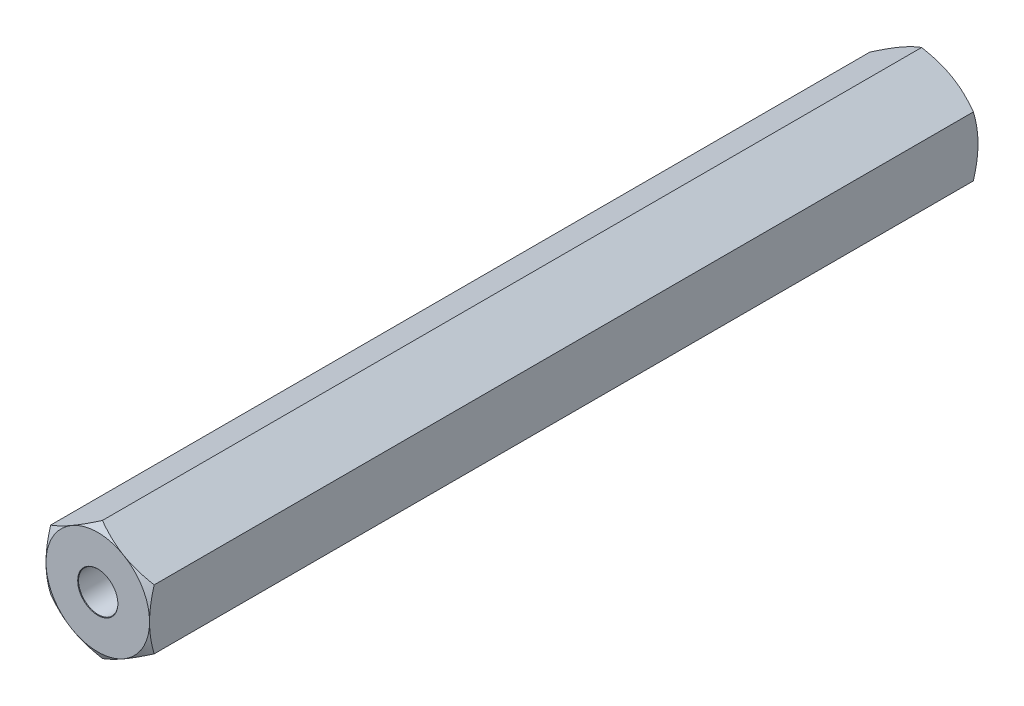
SolidWorks part; units mm, degrees
material "2011 Alloy"
ref_plane "Front Plane" through (0, 0, 0) normal (0, 0, 1) x (1, 0, 0)
ref_plane "Top Plane" through (0, 0, 0) normal (0, 1, 0) x (1, 0, 0)
ref_plane "Right Plane" through (0, 0, 0) normal (1, 0, 0) x (0, 0, -1)
sketch "Sketch3" plane through (0, 0, 0) normal (1, 0, 0) x (0, 0, -1)
  line L0 (-50.8, 0) -> (50.8, 0) construction
  line L1 (0, 6.35) -> (0, -6.35) construction
  line L2 (-50.8, 2.413) -> (-50.8, -2.413) construction
  point P2 (38.1, 0)
  point P3 (-38.1, 0)
  dimension "Length" = 101.6
  dimension "Min Thread Length" = 12.7
  dimension "D1" = 12.7
  dimension "Thread Dia" = 4.826
  dimension "Hex" = 12.7
sketch "Sketch1" plane through (0, 0, 0) normal (0, 0, 1) x (1, 0, 0)
  line L1 (0, 7.3323) -> (-6.35, 3.6662)
  line L2 (-6.35, 3.6662) -> (-6.35, -3.6662)
  line L3 (-6.35, -3.6662) -> (0, -7.3323)
  line L4 (0, -7.3323) -> (6.35, -3.6662)
  line L5 (6.35, -3.6662) -> (6.35, 3.6662)
  line L6 (6.35, 3.6662) -> (0, 7.3323)
  circle A0 centre (0, 0) radius 6.35 construction
  circle A1 centre (0, 0) radius 2.413
extrude "Extrude1" add sketch "Sketch1" along normal up to vertex (50.8 mm away) and the other way up to vertex (50.8 mm away) up to point (0, 0, 50.8) other way up to point (0, 0, -50.8)
sketch "Sketch11" plane through (0, 0, -50.8) normal (0, 0, -1) x (-1, 0, 0)
  circle A0 centre (0, 0) radius 2.413 construction
  circle A1 centre (0, 0) radius 2.413
curve "Helix/Spiral1" pitch 0.7937 height 102.3937 turns 129 parameters "Pitch"=0.7937
sketch "Sketch12" plane through (0, 0, 0) normal (1, 0, 0) x (0, 0, -1)
  line L0 (51.4945, 2.413) -> (50.8, 2.413)
  line L1 (51.4945, 2.413) -> (51.1969, 1.8974)
  line L2 (51.1969, 1.8974) -> (51.0977, 1.8974)
  line L3 (51.0977, 1.8974) -> (50.8, 2.413)
  line L4 (51.1473, 1.8974) -> (51.1473, 2.413) construction
  line L5 (51.3457, 2.1552) -> (50.9488, 2.1552) construction
  dimension "D1" = 0.0992
  dimension "D2" = 0.3969
  dimension "D3" = 60
sweep "Sweep1" [suppressed] add profiles "Sketch12" path "Helix/Spiral1"
sketch "Sketch6" plane through (0, 0, -50.8) normal (0, 0, -1) x (-1, 0, 0)
  line L6 (0, 7.3323) -> (-6.35, 3.6662)
  line L7 (-6.35, 3.6662) -> (-6.35, -3.6662)
  line L8 (-6.35, -3.6662) -> (0, -7.3323)
  line L9 (0, -7.3323) -> (6.35, -3.6662)
  line L10 (6.35, -3.6662) -> (6.35, 3.6662)
  line L11 (6.35, 3.6662) -> (0, 7.3323)
  line L12 (0, 7.3323) -> (-6.35, 3.6662)
  line L13 (-6.35, 3.6662) -> (-6.35, -3.6662)
  line L14 (-6.35, -3.6662) -> (0, -7.3323)
  line L15 (0, -7.3323) -> (6.35, -3.6662)
  line L16 (6.35, -3.6662) -> (6.35, 3.6662)
  line L17 (6.35, 3.6662) -> (0, 7.3323)
  dimension "D1" = 0
extrude "Extrude2" [suppressed] cut sketch "Sketch6" along normal through all
sketch "Sketch7" plane through (0, 0, -50.8) normal (0, 0, -1) x (-1, 0, 0)
  circle A2 centre (0, 0) radius 2.4638
  circle A3 centre (0, 0) radius 2.4638
  dimension "D1" = 0.0508
extrude "Extrude3" cut sketch "Sketch7" against normal through all draft 43
sketch "Sketch8" plane through (0, 0, -50.8) normal (0, 0, -1) x (-1, 0, 0)
  circle A0 centre (0, 0) radius 6.35 construction
  circle A1 centre (0, 0) radius 6.35
extrude "Extrude4" cut sketch "Sketch8" against normal through all draft 60 flip side to cut
mirror "Mirror1" about plane through (0, 0, 0) normal (0, 0, 1) of "Extrude2", "Extrude3", "Extrude4"
sketch "Sketch9" [suppressed] plane through (0, 0, 0) normal (1, 0, 0) x (0, 0, -1)
  line L1 (-38.1, 2.4638) -> (38.1, 2.4638)
  line L2 (-38.1, 2.4638) -> (-38.1, 0)
  line L3 (-38.1, 0) -> (38.1, 0)
  line L4 (38.1, 2.4638) -> (38.1, 0)
  line L7 (-50.8, 0) -> (50.8, 0) construction
revolve "Revolve" [suppressed] add sketch "Sketch9" angle 360 about L0
sketch "Sketch10" [suppressed] plane through (0, 0, 0) normal (1, 0, 0) x (0, 0, -1)
  line L0 (50.8, 2.413) -> (38.1, 2.413)
  line L1 (-50.8, 2.413) -> (-38.1, 2.413)
  line L2 (38.1, 2.413) -> (38.1, -2.413)
  line L3 (-50.8, -2.4638) -> (-38.1, -2.4638)
  line L4 (-38.1, 2.413) -> (-38.1, -2.4638)
  line L5 (38.1, -2.413) -> (50.8, -2.413)
equation "\"D1@Sketch3\" = \"Min Thread Length@Sketch3\""
equation "\"D3@Helix/Spiral1\" = \"Length@Sketch3\"+\"Pitch@Helix/Spiral1\""
equation "\"D1@Sketch12\" = \"Pitch@Helix/Spiral1\"*.125"
equation "\"D2@Sketch12\" = \"Pitch@Helix/Spiral1\"*.5"
